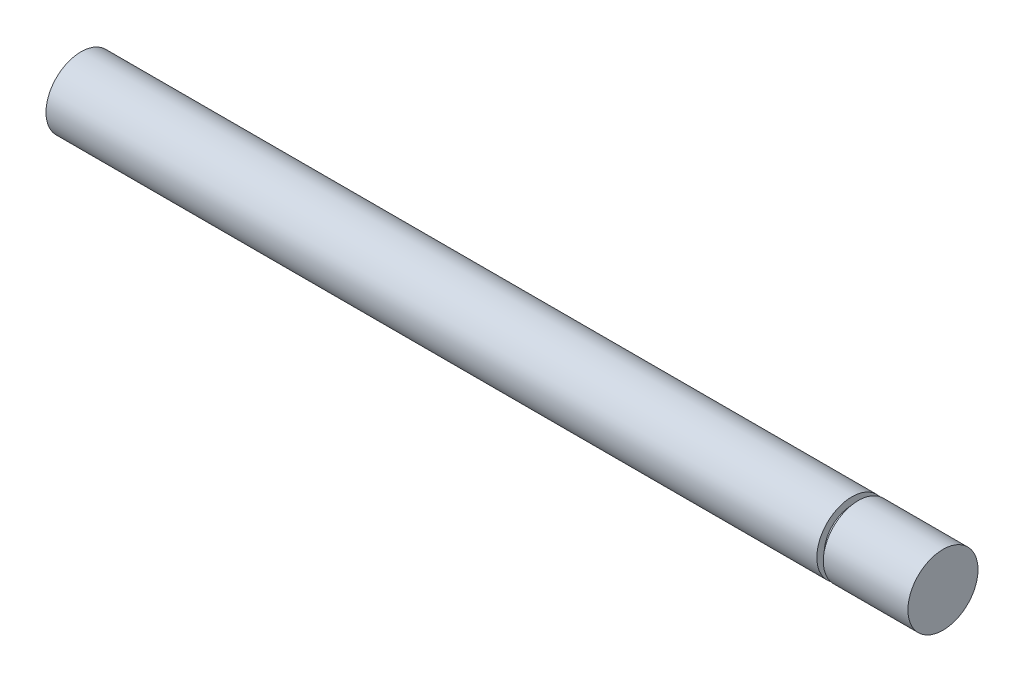
SolidWorks part; units mm, degrees
ref_plane "Front Plane" through (0, 0, 0) normal (0, 0, 1) x (1, 0, 0)
ref_plane "Top Plane" through (0, 0, 0) normal (0, 1, 0) x (1, 0, 0)
ref_plane "Right Plane" through (0, 0, 0) normal (1, 0, 0) x (0, 0, -1)
sketch "Sketch1" plane through (0, 0, 0) normal (1, 0, 0) x (0, 0, -1)
  circle A0 centre (0, 0) radius 6.35
  dimension "D1" = 12.7
extrude "Boss-Extrude1" add sketch "Sketch1" along normal mid plane 139.7
sketch "Sketch3" plane through (69.85, 0, 0) normal (1, 0, 0) x (0, 0, -1)
  circle A1 centre (0, 0) radius 6.35
  circle A2 centre (0, 0) radius 6.35
  dimension "D1" = 0
extrude "Boss-Extrude2" add sketch "Sketch3" along normal blind 16.51
sketch "Sketch2" plane through (0, 0, 0) normal (0, 0, 1) x (1, 0, 0)
  line L0 (0, 0) -> (86.36, 0) construction
  line L1 (71.0184, 5.0292) -> (69.85, 5.0292)
  line L2 (71.0184, 5.0292) -> (71.0184, 6.35)
  line L3 (71.0184, 6.35) -> (69.85, 6.35)
  line L4 (69.85, 5.0292) -> (69.85, 6.35)
  line L6 (86.36, 6.35) -> (-69.85, 6.35) construction
  line L8 (86.36, -6.35) -> (86.36, 6.35) construction
  dimension "D2" = 10.0584
  dimension "D3" = 16.51
revolve "Cut-Revolve1" cut sketch "Sketch2" angle 360 about L0
hole_wizard "1/4-20 Tapped Hole1" positions "Sketch8" profile "Sketch10" tap size "1/4-20" standard "ANSI Inch"
sketch "Sketch8" plane through (-69.85, 0, 0) normal (-1, 0, 0) x (0, 0, 1)
  point P0 (0, 0)
sketch "Sketch10" plane through (-69.85, 0, 0) normal (0, 1, 0) x (0, 0, 1)
  line L0 (0, 0) -> (0, 18.0438)
  line L1 (0, 18.0438) -> (2.5527, 16.51)
  line L2 (2.5527, 16.51) -> (2.5527, 0)
  line L5 (2.5527, 0) -> (0, 0)
  line L10 (0, 18.0438) -> (-2.5527, 16.51) construction
  line L11 (0, -6.35) -> (0, 107.95) construction
  dimension "Tap Drill Dia." = 5.1054
  dimension "Tap Drill Depth" = 16.51
  dimension "Drill Angle" = 118
cosmetic thread "Hole Thread1" parameters "D1"=12.7, "D2"=6.35
equation "\"ShaftDia\"=0.5"
equation "\"D1\"= \"YokeWidth\""
equation "\"EncoderWidth\"=0.65"
equation "\"D1@Boss-Extrude2\"=\"EncoderWidth\""
equation "\"D3@Sketch2\"=\"EncoderWidth\""
